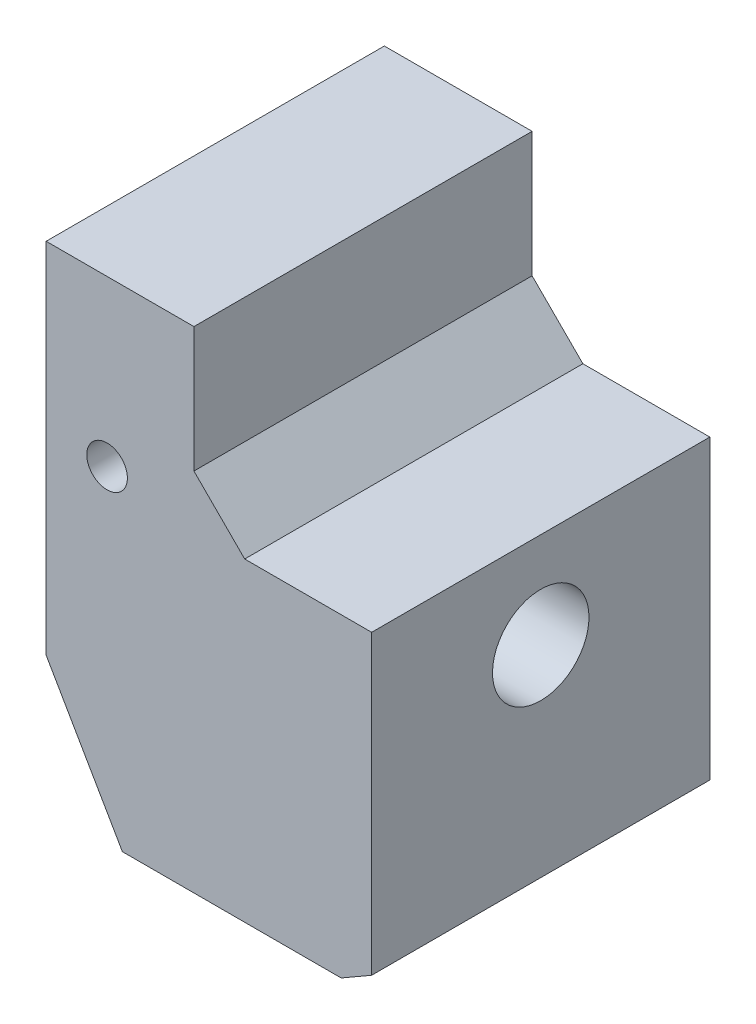
SolidWorks part; units mm, degrees
ref_plane "Front Plane" through (0, 0, 0) normal (0, 0, 1) x (1, 0, 0)
ref_plane "Top Plane" through (0, 0, 0) normal (0, 1, 0) x (1, 0, 0)
ref_plane "Right Plane" through (0, 0, 0) normal (1, 0, 0) x (0, 0, -1)
sketch "Sketch1" plane through (0, 0, 0) normal (1, 0, 0) x (0, 0, -1)
  line L1 (-16.65, 24.15) -> (16.65, 24.15)
  line L2 (-16.65, 24.15) -> (-16.65, -24.15)
  line L3 (-16.65, -24.15) -> (16.65, -24.15)
  line L4 (16.65, 24.15) -> (16.65, -24.15)
  line L5 (-16.65, 24.15) -> (16.65, -24.15) construction
  line L6 (-16.65, -24.15) -> (16.65, 24.15) construction
  point P0 (0, 0)
  dimension "D1" = 48.3
  dimension "D2" = 33.3
extrude "Boss-Extrude1" add sketch "Sketch1" along normal blind 9.55
sketch "Sketch2" plane through (0, 0, 0) normal (-1, 0, 0) x (0, 0, 1)
  line L0 (0, 24.15) -> (0, 19.15) construction
  line L1 (-4.5, 12.6332) -> (-4.5, 19.15)
  line L2 (-4.5, 12.6332) -> (-5.65, 11.45)
  line L3 (-16.65, 24.15) -> (16.65, 24.15) construction
  line L4 (0, 19.15) -> (0, -19.451) construction
  line L5 (0, -19.451) -> (0, -24.15) construction
  line L6 (16.65, -24.15) -> (-16.65, -24.15) construction
  line L7 (4.5, 19.15) -> (5.65, 19.15)
  line L8 (-11.65, -9.1) -> (-11.65, -0.8374)
  line L9 (-11.65, -9.95) -> (11.65, -9.95)
  line L10 (-5.5, 13.0391) -> (-5.5, 20.15)
  line L11 (4.5, 20.15) -> (-5.5, 20.15)
  line L12 (-11.65, -9.95) -> (-11.65, -9.1)
  line L13 (4.5, 20.15) -> (6.65, 20.15)
  line L14 (11.65, -9.95) -> (11.65, -9.1)
  line L15 (6.65, 20.15) -> (6.65, 5.9938)
  line L16 (6.65, 5.9938) -> (12.65, -0.4436)
  line L17 (12.65, -0.4436) -> (12.65, -9.1)
  line L18 (12.65, -10.95) -> (12.65, -9.1)
  line L19 (4.5, 19.15) -> (-4.5, 19.15)
  line L20 (-5.65, 5.6) -> (-5.65, 11.45)
  line L21 (-5.65, 5.6) -> (-11.65, -0.8374)
  line L22 (-12.65, -10.95) -> (12.65, -10.95)
  line L23 (-12.65, -10.95) -> (-12.65, -9.1)
  line L24 (-12.65, -9.1) -> (-12.65, -0.4436)
  line L25 (11.65, -0.8374) -> (11.65, -9.1)
  line L26 (5.65, 5.6) -> (11.65, -0.8374)
  line L27 (5.65, 19.15) -> (5.65, 5.6)
  line L28 (-6.65, 5.9938) -> (-12.65, -0.4436)
  line L29 (-6.65, 5.9938) -> (-6.65, 11.8559)
  line L30 (-5.5, 13.0391) -> (-6.65, 11.8559)
  point P16 (0, -10.1)
  dimension "D1" = 5
  dimension "D2" = 4.699
  dimension "D3" = 23.3
  dimension "D4" = 15.55
  dimension "D5" = 11.3
  dimension "D6" = 1.65
  dimension "D7" = 8.8
  dimension "D8" = 13.55
  dimension "D9" = 1
  dimension "D11" = 4.5
extrude "Cut-Extrude1" cut sketch "Sketch2" against normal blind 5.5 contours L27 L7 L19 L1 L2 L20 L21 L8 L12 L9 L14 L25 L26 | L10 L30 L29 L28 L24 L23 L22 L18 L17 L16 L15 L13 L11 L7 L27 L26 L25 L14 L9 L12 L8 L21 L20 L2 L1 L19 region at (0, 1.8051, 0.0888) region at (0, 16.5946, -5.0991)
sketch "Sketch3" plane through (5.5, 0, 0) normal (-1, 0, 0) x (0, 0, 1)
  line L0 (5.65, 19.15) -> (-4.5, 19.15)
  line L1 (-5.65, 5.45) -> (5.65, 5.45)
  line L2 (-5.65, 11.45) -> (-4.5, 12.6332)
  line L3 (-4.5, 12.6332) -> (-4.5, 19.15)
  line L4 (-5.65, 11.45) -> (-5.65, 5.45)
  line L5 (6.65, 20.15) -> (-5.5, 20.15)
  line L6 (0, 5.45) -> (0, 19.15) construction
  line L7 (-5.5, 13.0391) -> (-5.5, 20.15)
  line L8 (-6.65, 11.8559) -> (-5.5, 13.0391)
  line L9 (-6.65, 11.8559) -> (-6.65, 4.45)
  line L10 (-6.65, 4.45) -> (6.65, 4.45)
  line L11 (5.65, 5.45) -> (5.65, 19.15)
  line L12 (6.65, 4.45) -> (6.65, 20.15)
  dimension "D1" = 1
extrude "Cut-Extrude2" cut sketch "Sketch3" against normal blind 5 contours L6 L1 L11 L0 | L1 L6 L0 L3 L2 L4 | L10 L12 L5 L7 L8 L9 L11 L1 L4 L2 L3 L0 region at (5.5, 12.3, 2.825) region at (5.5, 11.9118, -2.5574) region at (5.5, 12.3, 6.4442)
sketch "Sketch5" plane through (9.55, 0, 0) normal (1, 0, 0) x (0, 0, -1)
  line L1 (-16.65, 24.15) -> (16.65, 24.15)
  line L2 (-16.65, 24.15) -> (-16.65, -24.15)
  line L3 (-16.65, -24.15) -> (16.65, -24.15)
  line L4 (16.65, 24.15) -> (16.65, -24.15)
  line L5 (-16.65, 24.15) -> (16.65, -24.15) construction
  line L6 (-16.65, -24.15) -> (16.65, 24.15) construction
  point P0 (0, 0)
extrude "Boss-Extrude3" add sketch "Sketch5" along normal blind 22.5
sketch "Sketch6" plane through (5.5, 0, 0) normal (-1, 0, 0) x (0, 0, 1)
  line L0 (0, 5.45) -> (0, -2.575) construction
  line L1 (-5.65, 5.45) -> (5.65, 5.45) construction
  line L2 (0, 1.45) -> (5.4752, 1.45) construction
  circle A0 centre (0, -2.575) radius 4.025
  dimension "D2" = 8.05
  dimension "D1" = 4
extrude "Cut-Extrude3" cut sketch "Sketch6" against normal blind 12
sketch "Sketch7" plane through (17.5, 0, 0) normal (-1, 0, 0) x (0, 0, 1)
  circle A0 centre (0, -2.575) radius 4.75
  dimension "D1" = 9.5
extrude "Cut-Extrude4" cut sketch "Sketch7" against normal up to surface (14.55 mm away) up to face at (32.05, 0, 0)
sketch "Sketch27" plane through (0, 0, 5.65) normal (0, 0, -1) x (-1, 0, 0)
  circle A0 centre (-6, 7.95) radius 2
  dimension "D1" = 4
  dimension "D2" = 6
extrude "Cut-Extrude6" cut sketch "Sketch27" against normal through all both and the other way through all
ref_plane "Plane1" through (18.4698, -31.9906, 0) normal (0.5, -0.866, 0) x (0, 0, -1)
sketch "Sketch28" plane through (0, 0, 0) normal (0, 0, 1) x (1, 0, 0)
  line L0 (32.05, -2.575) -> (17.5, -2.575) construction
  line L1 (32.05, -7.325) -> (32.05, 2.175) construction
  line L2 (17.5, -6.6) -> (17.5, 1.45) construction
  line L3 (17.5, -2.575) -> (17.5, -6.6) construction
  line L4 (17.5, -7.325) -> (17.5, 2.175) construction
  line L5 (17.5, -6.6) -> (13.5, -6.6) construction
  line L6 (13.5, -6.6) -> (25.7369, -27.7949)
  line L7 (3.2039, -40.8043) -> (33.7356, -23.1768) construction
  line L8 (13.5, -6.6) -> (11.25, -2.7029)
  dimension "D1" = 4.025
  dimension "D2" = 4
  dimension "D3" = 60
  dimension "D4" = 180
  dimension "D5" = 4.5
sketch "Sketch29" plane through (0, 0, 0) normal (0, 0, 1) x (1, 0, 0)
  line L0 (32.05, -2.575) -> (17.5, -2.575) construction
  line L1 (32.05, -7.325) -> (32.05, 2.175) construction
  line L2 (19.5, -16.9923) -> (25.7369, -27.7949)
  line L3 (17.5, -2.575) -> (17.5, -6.6) construction
  line L4 (3.2039, -40.8043) -> (33.7356, -23.1768) construction
  line L5 (17.5, -6.6) -> (13.5, -6.6) construction
  line L6 (13.5, -6.6) -> (19.5, -16.9923) construction
  line L8 (13.5, -6.6) -> (25.7369, -27.7949) construction
  dimension "D1" = 4.025
  dimension "D2" = 4
  dimension "D3" = 12
  dimension "D4" = 60
sketch "Sketch30" plane through (18.4698, -31.9906, 0) normal (0.5, -0.866, 0) x (0, 0, -1)
  circle A0 centre (0, 8.3913) radius 4
  dimension "D1" = 8
sweep "Cut-Sweep1" cut profiles "Sketch30" path "Sketch28"
sketch "Sketch31" plane through (18.4698, -31.9906, 0) normal (0.5, -0.866, 0) x (0, 0, -1)
  circle A0 centre (0, 8.3913) radius 5
  dimension "D1" = 10
sweep "Cut-Sweep2" cut profiles "Sketch31" path "Sketch29"
chamfer "Chamfer1" distance 13 angle 30 1 edges at (0, -24.15, 0) first distance on face at (0, 0, 0)
chamfer "Chamfer2" distance 10 angle 60 1 edges at (32.05, 24.15, 0) first distance on face at (16.025, 24.15, 0)
chamfer "Chamfer3" distance 3 angle 30 1 edges at (32.05, -24.15, 0) first distance on face at (29.406, -24.15, 0)
sketch "Croquis2" plane through (0, 0, 16.65) normal (0, 0, 1) x (1, 0, 0)
  line L0 (32.05, 6.8295) -> (14.55, 6.8295)
  line L1 (14.55, 6.8295) -> (14.55, 24.15)
  line L2 (22.05, 24.15) -> (0, 24.15) construction
  line L3 (14.55, 24.15) -> (32.05, 24.15)
  line L4 (32.05, 24.15) -> (32.05, 6.8295)
  dimension "D1" = 17.5
  dimension "D2" = 17.5
extrude "Cortar-Extruir1" cut sketch "Croquis2" against normal blind 48
chamfer "Chamfer4" distance 5 angle 45 1 edges at (14.55, 6.8295, 0)
sketch "Sketch33" plane through (0, 0, 0) normal (-1, 0, 0) x (0, 0, 1)
  line L0 (0, -9.95) -> (0, -15.45)
  line L1 (-11.65, -9.95) -> (11.65, -9.95) construction
  line L2 (0, -15.45) -> (2.5, -15.45)
  line L3 (2.5, -15.45) -> (2.5, -9.95)
  line L4 (-11.65, -9.95) -> (11.65, -9.95) construction
  line L5 (2.5, -9.95) -> (0, -9.95)
  dimension "D1" = 5.5
  dimension "D2" = 2.5
sketch "Sketch34" plane through (5.5, 0, 0) normal (-1, 0, 0) x (0, 0, 1)
  line L0 (0, -9.95) -> (2.5, -9.95)
  line L1 (-11.65, -9.95) -> (11.65, -9.95) construction
  line L2 (2.5, -9.95) -> (2.5, -10.45)
  line L3 (2.5, -10.45) -> (0, -10.45)
  line L4 (0, -10.45) -> (0, -9.95)
  dimension "D1" = 0.5
loft "Cut-Loft2" cut profiles "Sketch33", "Sketch34" connector at (0, -15.45, 2.5) connector at (5.5, -10.45, 2.5)
